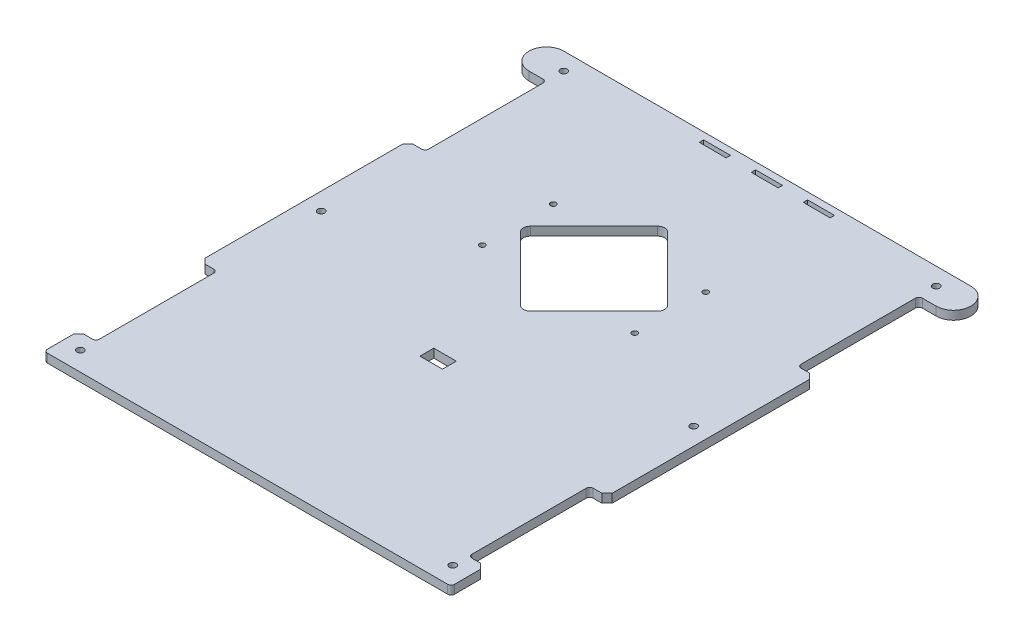
SolidWorks part; units mm, degrees
material "Teak"
ref_plane "Front Plane" through (0, 0, 0) normal (0, 0, 1) x (1, 0, 0)
ref_plane "Top Plane" through (0, 0, 0) normal (0, 1, 0) x (1, 0, 0)
ref_plane "Right Plane" through (0, 0, 0) normal (1, 0, 0) x (0, 0, -1)
sketch "Sketch1" plane through (0, 0, 0) normal (0, 1, 0) x (1, 0, 0)
  line L0 (0, 190) -> (0, -110) construction
  line L1 (-117.5, 0) -> (117.5, 0) construction
  line L2 (-117.5, -110) -> (117.5, -110)
  line L3 (117.5, -110) -> (117.5, -90)
  line L4 (117.5, -90) -> (107.5, -90)
  line L5 (107.5, -90) -> (107.5, -20)
  line L6 (107.5, -20) -> (117.5, -20)
  line L7 (117.5, -20) -> (117.5, 100)
  line L8 (117.5, 100) -> (107.5, 100)
  line L9 (107.5, 100) -> (107.5, 170)
  line L10 (107.5, 170) -> (127.5, 170)
  line L11 (-107.5, 170) -> (-127.5, 170)
  line L12 (-107.5, 100) -> (-107.5, 170)
  line L13 (-117.5, 100) -> (-107.5, 100)
  line L14 (-117.5, -20) -> (-117.5, 100)
  line L15 (-107.5, -20) -> (-117.5, -20)
  line L16 (-107.5, -90) -> (-107.5, -20)
  line L17 (-117.5, -90) -> (-107.5, -90)
  line L18 (-117.5, -110) -> (-117.5, -90)
  line L19 (127.5, 170) -> (127.5, 190)
  line L20 (127.5, 190) -> (-127.5, 190)
  line L21 (-127.5, 170) -> (-127.5, 190)
  point P5 (0, 0)
  dimension "D1" = 20
  dimension "D2" = 300
  dimension "D3" = 110
  dimension "D4" = 20
  dimension "D5" = 10
  dimension "D6" = 70
  dimension "D7" = 70
  dimension "D8" = 255
  dimension "D9" = 20
extrude "Boss-Extrude1" add sketch "Sketch1" along normal blind 5
fillet "Fillet3" 2 edges at (127.5, 2.5, -170) (127.5, 2.5, -190) type full round first side face at (117.5, 2.5, -170) second side face at (0, 2.5, -190) middle face at (127.5, 2.5, -180)
fillet "Fillet4" 2 edges at (-127.5, 2.5, -190) (-127.5, 2.5, -170) type full round first side face at (-5, 2.5, -190) second side face at (-117.5, 2.5, -170) middle face at (-127.5, 2.5, -180)
fillet "Fillet2" radius 2 10 edges at (107.5, 2.5, 20) (107.5, 2.5, -170) (107.5, 2.5, -100) (107.5, 2.5, 90) (-107.5, 2.5, -100) (-107.5, 2.5, 90) (-107.5, 2.5, 20) (-107.5, 2.5, -170) (-117.5, 2.5, 110) (117.5, 2.5, 110)
sketch "Sketch2" plane through (0, 5, 0) normal (0, 1, 0) x (1, 0, 0)
  line L0 (0, -110) -> (0, 90) construction
  line L1 (-115.5, -110) -> (115.5, -110) construction
  line L2 (107.5, 102) -> (107.5, 168) construction
  line L4 (117.5, -20) -> (117.5, 100) construction
  line L5 (117.5, -108) -> (117.5, -90) construction
  arc A0 (117.5, 170) -> (117.5, 190) centre (117.5, 180) ccw construction
  circle A1 centre (107.5, 180) radius 2
  circle A2 centre (107.5, 40) radius 2
  circle A3 centre (107.5, -99) radius 2
  circle A5 centre (-107.5, -99) radius 2
  circle A6 centre (-107.5, 40) radius 2
  circle A7 centre (-107.5, 180) radius 2
  point P17 (127.5, 180)
  point P26 (117.5, 40)
  point P30 (117.5, -99)
  dimension "D1" = 4
  dimension "D3" = 10
extrude "layer fix hole" cut sketch "Sketch2" against normal through all
sketch "Sketch3" plane through (0, 5, 0) normal (0, 1, 0) x (1, 0, 0)
  line L0 (0, 190) -> (0, -110) construction
  line L1 (117.5, 190) -> (-117.5, 190) construction
  line L2 (-115.5, -110) -> (115.5, -110) construction
  line L3 (-39.598, 92.8284) -> (-2.8284, 129.598)
  line L8 (-50, 116.5) -> (50, 116.5) construction
  line L9 (-50, 116.5) -> (-50, 63.5) construction
  line L14 (-50, 63.5) -> (50, 63.5) construction
  line L15 (50, 116.5) -> (50, 63.5) construction
  line L21 (-50, 116.5) -> (50, 63.5) construction
  line L22 (-50, 63.5) -> (50, 116.5) construction
  line L23 (-39.598, 87.1716) -> (-2.8284, 50.402)
  line L24 (2.8284, 129.598) -> (39.598, 92.8284)
  line L25 (2.8284, 50.402) -> (39.598, 87.1716)
  line L26 (-35.0018, 90) -> (39.9515, 90) construction
  line L27 (0, 127.4767) -> (0, 52.5233) construction
  circle A12 centre (44, 110.5) radius 1.6
  circle A13 centre (44, 69.5) radius 1.6
  circle A14 centre (-44, 69.5) radius 1.6
  circle A15 centre (-44, 110.5) radius 1.6
  arc A16 (-2.8284, 129.598) -> (2.8284, 129.598) centre (0, 126.7696) cw
  arc A17 (39.598, 92.8284) -> (39.598, 87.1716) centre (36.7696, 90) cw
  arc A18 (-2.8284, 50.402) -> (2.8284, 50.402) centre (0, 53.2304) ccw
  arc A19 (-39.598, 87.1716) -> (-39.598, 92.8284) centre (-36.7696, 90) cw
  point P6 (0, 90)
  point P19 (0, 0)
  point P20 (0, 90)
  point P21 (-21.2132, 111.2132)
  point P22 (21.2132, 68.7868)
  point P23 (0, 0)
  point P24 (0, 0)
  dimension "D3" = 3.2
  dimension "D2" = 100
  dimension "D9" = 6
  dimension "D14" = 4
  dimension "D1" = 53
  dimension "D4" = 6
  dimension "D5" = 6
  dimension "D6" = 6
  dimension "D7" = 6
  dimension "D8" = 6
  dimension "D10" = 6
  dimension "D11" = 6
  dimension "D12" = 60
  dimension "D13" = 100
extrude "arm fix hole" cut sketch "Sketch3" against normal through all
sketch "Sketch4" plane through (0, 5, 0) normal (0, 1, 0) x (1, 0, 0)
  line L0 (0, 0) -> (0, 190) construction
  line L1 (117.5, 190) -> (-117.5, 190) construction
  line L2 (-32.75, 186) -> (-32.75, 183.5)
  line L3 (-72.75, 186) -> (-57.25, 186)
  line L4 (-72.75, 186) -> (-72.75, 183.5)
  line L5 (-72.75, 183.5) -> (-57.25, 183.5)
  line L6 (-57.25, 186) -> (-57.25, 183.5)
  line L7 (-17.25, 183.5) -> (-32.75, 183.5)
  line L8 (-17.25, 186) -> (-17.25, 183.5)
  line L9 (-17.25, 186) -> (-32.75, 186)
  line L10 (5, 97.0905) -> (5, 68.2589) construction
  line L11 (-85, 183.5) -> (85, 183.5) construction
  line L12 (-85, 183.5) -> (-85, 186) construction
  line L13 (-85, 186) -> (85, 186) construction
  line L14 (85, 183.5) -> (85, 186) construction
  line L15 (-25, 68.2589) -> (-25, 97.0905) construction
  line L16 (-65, 97.0905) -> (-65, 68.2589) construction
  line L17 (-25, 68.2589) -> (-25, 97.0905) construction
  line L18 (35, 68.2589) -> (35, 97.0905) construction
  line L20 (-2.75, 183.5) -> (12.75, 183.5)
  line L21 (-2.75, 183.5) -> (-2.75, 186)
  line L22 (-2.75, 186) -> (12.75, 186)
  line L23 (12.75, 183.5) -> (12.75, 186)
  line L24 (27.25, 183.5) -> (42.75, 183.5)
  line L25 (27.25, 183.5) -> (27.25, 186)
  line L26 (27.25, 186) -> (42.75, 186)
  line L27 (42.75, 183.5) -> (42.75, 186)
  point P17 (-65, 183.5)
  point P25 (-25, 183.5)
  point P35 (5, 186)
  point P36 (35, 186)
  dimension "D1" = 15.5
  dimension "D2" = 2.5
  dimension "D3" = 4
  dimension "D4" = 20
  dimension "D5" = 170
  dimension "D6" = 60
  dimension "D7" = 90
  dimension "D8" = 120
extrude "IR fix hole" cut sketch "Sketch4" against normal through all
chamfer "Chamfer1" distance 3 angle 45 6 edges at (117.5, 2.5, 20) (-117.5, 2.5, -100) (-117.5, 2.5, 20) (-117.5, 2.5, 90) (117.5, 2.5, -100) (117.5, 2.5, 90)
sketch "Sketch5" plane through (0, 5, 0) normal (0, 1, 0) x (1, 0, 0)
  line L1 (-57.25, 183.5) -> (-72.75, 183.5)
  line L2 (-57.25, 183.5) -> (-57.25, 186)
  line L3 (-57.25, 186) -> (-72.75, 186)
  line L4 (-72.75, 183.5) -> (-72.75, 186)
extrude "Boss-Extrude2" add sketch "Sketch5" against normal up to surface (5 mm away) up to face at (-65, 0, -184.75)
sketch "Sketch6" plane through (0, 5, 0) normal (0, 1, 0) x (1, 0, 0)
  line L0 (0, 110) -> (0, -110) construction
  line L1 (-115.5, -110) -> (115.5, -110) construction
  line L3 (6.5, -4) -> (-6.5, -4)
  line L4 (6.5, -4) -> (6.5, 4)
  line L5 (6.5, 4) -> (-6.5, 4)
  line L6 (-6.5, -4) -> (-6.5, 4)
  line L7 (6.5, -4) -> (-6.5, 4) construction
  line L8 (6.5, 4) -> (-6.5, -4) construction
  point P0 (0, 0)
  point P6 (0, 0)
  dimension "D1" = 13
  dimension "D2" = 8
extrude "Turn on/off Switch " cut sketch "Sketch6" against normal up to next
